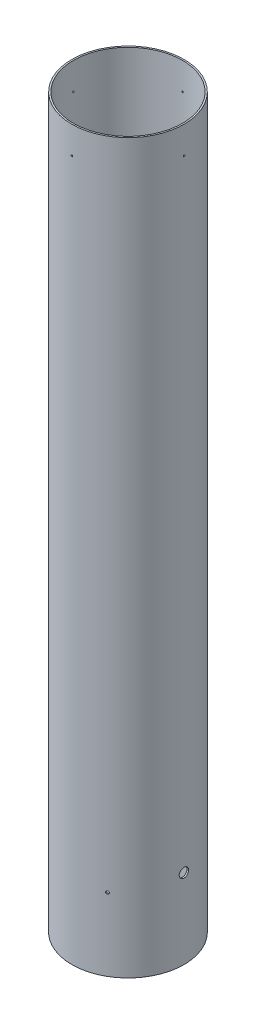
SolidWorks part; units mm, degrees
material "A-Glass Fiber"
ref_plane "Front Plane" through (0, 0, 0) normal (0, 0, 1) x (1, 0, 0)
ref_plane "Top Plane" through (0, 0, 0) normal (0, 1, 0) x (1, 0, 0)
ref_plane "Right Plane" through (0, 0, 0) normal (1, 0, 0) x (0, 0, -1)
sketch "Sketch1" plane through (0, 0, 0) normal (0, 1, 0) x (1, 0, 0)
  circle A0 centre (0, 0) radius 76.1746
  circle A1 centre (0, 0) radius 78.359
  dimension "D1" = 156.718
  dimension "D2" = 152.3492
extrude "Boss-Extrude1" add sketch "Sketch1" along normal blind 1016
ref_axis "Axis1" through (0, 1016, 0) along (0, -1, 0)
sketch "Sketch2" plane through (0, 0, 0) normal (1, 0, 0) x (0, 0, -1)
  line L0 (78.359, 1016) -> (-78.359, 1016) construction
  circle A0 centre (0, 977.9) radius 1.0922
  dimension "D1" = 2.1844
  dimension "D2" = 38.1
extrude "Cut-Extrude1" cut sketch "Sketch2" against normal through all
pattern_circular "CirPattern1" count 4 over 360 about axis through (0, 1016, 0) along (0, 1, 0) of "Cut-Extrude1"
hole_wizard "1/2 Clearance Hole1" positions "Sketch3" profile "Sketch4" hole size "1/2" standard "ANSI Inch"
sketch "Sketch3" plane through (0, 0, 0) normal (1, 0, 0) x (0, 0, -1)
  point P0 (0, 111.125)
  dimension "D1" = 111.125
sketch "Sketch4" plane through (0, 111.125, 0) normal (0, 1, 0) x (0, 0, 1)
  line L0 (0, 0) -> (0, 92.8345)
  line L1 (0, 92.8345) -> (6.5481, 88.9)
  line L2 (6.5481, 88.9) -> (6.5481, 0)
  line L5 (6.5481, 0) -> (0, 0)
  line L10 (0, 92.8345) -> (-6.5481, 88.9) construction
  line L11 (0, -6.35) -> (0, 107.95) construction
  dimension "Hole Dia." = 13.0962
  dimension "Hole Depth" = 88.9
  dimension "Drill Angle" = 118
hole_wizard "Ø4.0 (4) Diameter Hole1" positions "Sketch5" profile "Sketch6" hole size "Ø4.0" standard "ANSI Metric"
sketch "Sketch5" plane through (0, 0, 0) normal (1, 0, 0) x (0, 0, -1)
  point P0 (0, 101.6)
  dimension "D1" = 101.6
sketch "Sketch6" plane through (0, 101.6, 0) normal (0, 1, 0) x (0, 0, -1)
  line L0 (0, 0) -> (0, 90.1017)
  line L1 (0, 90.1017) -> (2, 88.9)
  line L2 (2, 88.9) -> (2, 0)
  line L5 (2, 0) -> (0, 0)
  line L10 (0, 90.1017) -> (-2, 88.9) construction
  line L11 (0, -6.35) -> (0, 107.95) construction
  dimension "Hole Dia." = 4
  dimension "Hole Depth" = 88.9
  dimension "Drill Angle" = 118
pattern_circular "CirPattern2" count 3 over 360 about axis through (0, 0, 0) along (0, 1, 0) of "Ø4.0 (4) Diameter Hole1"
equation "\"Fwd_Tube_Length\" = 40in"
equation "\"D1@Boss-Extrude1\" = \"Fwd_Tube_Length\""
equation "\"BKHD_Screw_Diam\"= 3.5mm"
equation "\"Fwd_BKHD_From_Top\" = 18in"
equation "\"Bodytube_OD\" = 6.17in"
equation "\"Bodytube_ID\" = 5.998in"
equation "\"D2@Sketch1\"=\"Bodytube_ID\""
equation "\"D1@Sketch1\"=\"Bodytube_OD\""
equation "\"Shear_Screw_Diameter\" = 0.086in"
equation "\"Shear_Screw_Coupler_Location\" = 4.5in"
equation "\"Motor_OD\" = 4in"
equation "\"Mid_Tube_Length\" = 1in"
equation "\"Mid_Coupler_Length\" = 13in"
equation "\"Aft_Section_Length\"= 39in"
equation "\"AB_Coupler_OD_Length\"= 1in"
equation "\"AB_Coupling_Section_Length\"= 0.375in"
equation "\"AB_Coupler_Length\"= \"AB_Coupler_OD_Length\" + \"AB_Coupling_Section_Length\" * 2"
equation "\"Cutout_Angle\" = 80"
equation "\"AB_Paddle_Height\" = 0.375in"
equation "\"AB_Coupler_Num_Screws\"= 4"
equation "\"AB_BKHD_Thickness\" = 0.375in"
equation "\"AB_Mount_From_Bottom\" = 23.175in"
equation "\"Num_Cutouts\" = 3"
equation "\"AB_Coupler_OD\"= 6.17in"
equation "\"AB_Coupler_ID\"= 5.75in"
equation "\"AB_Coupler_Surface_Diameter\"= 5.998in"
equation "\"AB_Coupling_Screw_Diameter\"= 0.15748in"
equation "\"AB_Central_Bushing_Length\" = .4724in"
equation "\"Lead_Screw_Dist\" = 3.4in"
equation "\"Lead_Screw_Diam\" = 0.386in"
equation "\"Lead_Screw_Length\" = (\"Mid_Coupler_Length\" + 2*0.375in + 2*0.5in)"
equation "\"Paddle_Pin_Offset\" = .25in"
equation "\"Paddle_Pin_Radius\" = 2.25in"
equation "\"SS_Paddle_Pin_Radius\" = 2.25*0.66in"
equation "\"Paddle_Gear_OD\" = 3.2in"
equation "\"Drive_Gear_OD\" = 1.7in"
equation "\"Fin_Thickness\"= .118in"
equation "\"Guiderail_Cutout_Diameter\"= 1.5in"
equation "\"DB9_Hole_Dist\" = 25mm"
equation "\"DB9_Relief_Width\" = 0.47in"
equation "\"DB9_Relief_Hole_Offset\" = 0.09in"
equation "\"Airbrakes_Wire_Hole_Dia\" = .25in"
equation "\"Airbrakes_Wire_Hole_Dist\" = 1.1in"
equation "\"Servo_Gear_Offset\" = 0.5in"
equation "\"D1@Sketch2\"=\"Shear_Screw_Diameter\""
equation "\"FWD_Shear_Screw_Dist\" = 1.5in"
equation "\"D2@Sketch2\"=\"FWD_Shear_Screw_Dist\""
